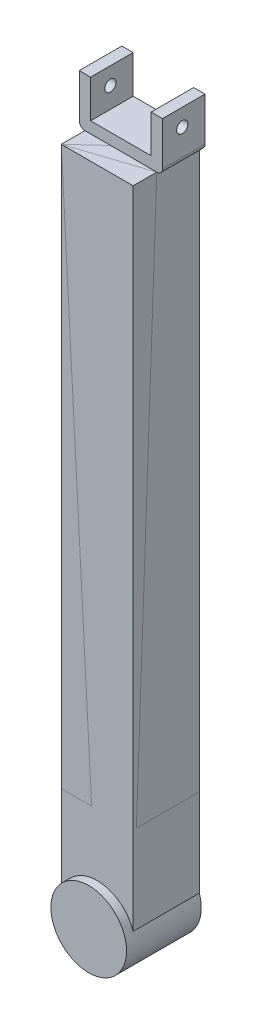
SolidWorks part; units mm, degrees
ref_plane "Front Plane" through (0, 0, 0) normal (0, 0, 1) x (1, 0, 0)
ref_plane "Top Plane" through (0, 0, 0) normal (0, 1, 0) x (1, 0, 0)
ref_plane "Right Plane" through (0, 0, 0) normal (1, 0, 0) x (0, 0, -1)
sketch "Sketch1" plane through (0, 0, 0) normal (0, 1, 0) x (1, 0, 0)
  line L1 (-19, 17.5) -> (19, 17.5)
  line L2 (-19, 17.5) -> (-19, -17.5)
  line L3 (-19, -17.5) -> (19, -17.5)
  line L4 (19, 17.5) -> (19, -17.5)
  line L5 (-19, 17.5) -> (19, -17.5) construction
  line L6 (-19, -17.5) -> (19, 17.5) construction
  point P0 (0, 0)
  dimension "D1" = 35
  dimension "D2" = 38
extrude "Boss-Extrude1" add sketch "Sketch1" against normal blind 295
sketch "Sketch2" plane through (0, 0, 0) normal (0, 0, 1) x (1, 0, 0)
  line L0 (-19, 0) -> (19, 0)
  line L1 (22, 3) -> (22, 26)
  line L2 (-22, 3) -> (-22, 26)
  line L3 (16, 6) -> (16, 26)
  line L4 (-16, 6) -> (16, 6)
  line L5 (-16, 6) -> (-16, 26)
  line L6 (-16, 26) -> (-22, 26)
  line L7 (16, 26) -> (22, 26)
  line L8 (-22, 0) -> (22, 0) construction
  line L9 (-22, 0) -> (-22, 26) construction
  line L10 (22, 0) -> (22, 26) construction
  arc A0 (-19, 0) -> (-22, 3) centre (-19, 3) cw
  arc A1 (19, 0) -> (22, 3) centre (19, 3) ccw
  dimension "D2" = 3
  dimension "D3" = 3
  dimension "D1" = 6
extrude "Boss-Extrude3" add sketch "Sketch2" against normal blind 17.5 and the other way blind 5 separate body
extrude "Boss-Extrude6" add sketch "Sketch1<3>" against normal blind 348.59
sketch "Sketch1<3>" plane through (0, 0, 0) normal (0, 1, 0) x (1, 0, 0) same geometry as "Sketch1"
ref_plane "Plane2" through (16, 0, 0) normal (-1, 0, 0) x (0, 0, 1)
sketch "Sketch3" plane through (16, 0, 0) normal (-1, 0, 0) x (0, 0, 1)
  circle A0 centre (-5.4606, 16.8963) radius 3
extrude "Cut-Extrude1" cut sketch "Sketch3" against normal up to vertex (6 mm away) up to point (22, 26, -17.5)
mirror "Mirror1" about plane through (0, 0, 0) normal (1, 0, 0) of "Cut-Extrude1"
ref_point "Point1"
ref_point "Point2"
ref_axis "Axis1" through (16, 16.8963, -5.4606) along (-1, 0, 0)
sketch "Sketch9" plane through (-16, 0, 0) normal (1, 0, 0) x (0, 0, -1)
  line L0 (5.4606, 16.8963) -> (17.5, 16.8963) construction
  line L1 (17.5, 6) -> (17.5, 26) construction
ref_plane "Plane3" through (0, 0, 0) normal (1, 0, 0) x (0, 0, -1)
ref_plane "Plane4" through (0, 16.8963, 0) normal (0, 1, 0) x (1, 0, 0)
ref_axis "Axis3" through (0, 16.8963, 49.053) along (0, 0, -1)
sketch "Sketch11" plane through (0, 16.8963, 0) normal (0, 1, 0) x (1, 0, 0)
  line L1 (0, -49.053) -> (0, 76.8789) construction
  line L2 (16, 5.4606) -> (-16, 5.4606) construction
  point P0 (0, 5.4606)
sketch "Sketch5" plane through (0, 0, 0) normal (0, 0, 1) x (1, 0, 0)
  line L0 (0, -74.8085) -> (0, 74.8085) construction
  line L1 (16, 16.8963) -> (-16, 16.8963) construction
  circle A0 centre (0, -347.6037) radius 20
  dimension "D1" = 364.5
extrude "Boss-Extrude8" add sketch "Sketch5" along normal blind 22 and the other way up to vertex (17.5 mm away) other way up to point (-19, -348.59, -17.5)
sketch "Sketch8" plane through (-19, 0, 0) normal (-1, 0, 0) x (0, 0, 1)
  line L0 (5, 0) -> (-17.5, 0) construction
  circle A0 centre (-5.4606, -85) radius 5
  dimension "D1" = 85
  dimension "D2" = 0
extrude "Cut-Extrude2" cut sketch "Sketch8" against normal blind 10
ref_plane "Plane5" through (0, 0, -5.4606) normal (0, 0, 1) x (1, 0, 0)
